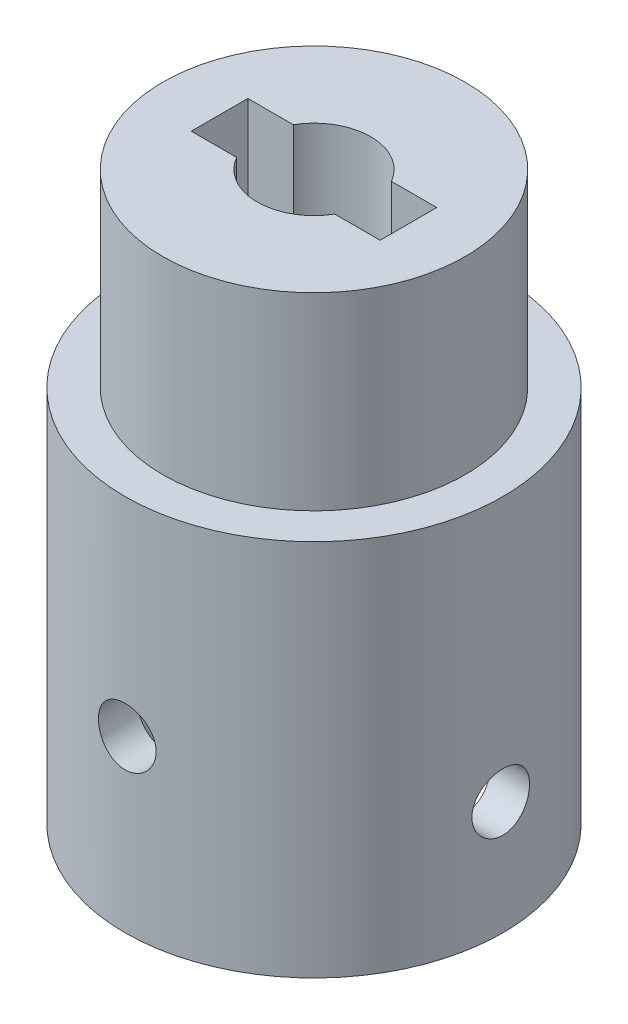
SolidWorks part; units mm, degrees
ref_plane "前视基准面" through (0, 0, 0) normal (0, 0, 1) x (1, 0, 0)
ref_plane "上视基准面" through (0, 0, 0) normal (0, 1, 0) x (1, 0, 0)
ref_plane "右视基准面" through (0, 0, 0) normal (1, 0, 0) x (0, 0, -1)
other "Configuration Table"
sketch "草图8" plane through (0, 0, 0) normal (0, 1, 0) x (1, 0, 0)
  circle A0 centre (79.6394, -3.747) radius 20
  circle A1 centre (79.6394, -3.747) radius 16
  dimension "D1" = 40
extrude "凸台-拉伸3" add sketch "草图8" along normal blind 20 separate body contours A1 region at (79.6394, 0, 3.747)
extrude "凸台-拉伸4" add sketch "草图8<4>" against normal blind 40 contours A0
sketch "草图8<4>" plane through (0, 0, 0) normal (0, 1, 0) x (1, 0, 0) same geometry as "草图8"
sketch "草图9" plane through (0, 20, 0) normal (0, 1, 0) x (1, 0, 0)
sketch "草图10" plane through (0, 20, 0) normal (0, 1, 0) x (1, 0, 0)
  line L0 (84.8356, -0.747) -> (89.6394, -0.747)
  line L1 (69.6394, -0.747) -> (74.4433, -0.747)
  line L2 (69.6394, -0.747) -> (69.6394, -6.747)
  line L3 (69.6394, -6.747) -> (74.4433, -6.747)
  line L4 (89.6394, -0.747) -> (89.6394, -6.747)
  line L5 (84.8356, -6.747) -> (89.6394, -6.747)
  arc A0 (74.4433, -6.747) -> (84.8356, -6.747) centre (79.6394, -3.747) ccw
  arc A1 (84.8356, -0.747) -> (74.4433, -0.747) centre (79.6394, -3.747) ccw
  dimension "D1" = 6
  dimension "D3" = 12
  dimension "D2" = 20
extrude "切除-拉伸6" cut sketch "草图10" against normal up to next
sketch "草图11" plane through (0, 0, 0) normal (0, 0, 1) x (1, 0, 0)
  line L0 (79.6394, -40) -> (79.6394, 0) construction
  line L2 (99.6394, 0) -> (59.6394, 0) construction
  circle A0 centre (79.6394, -22) radius 3.05
  dimension "D1" = 6.1
  dimension "D2" = 22
extrude "切除-拉伸7" cut sketch "草图11" against normal through all both and the other way through all
sketch "草图12" plane through (0, -40, 0) normal (0, -1, 0) x (1, 0, 0)
  circle A0 centre (79.6394, 3.747) radius 16.025
  dimension "D1" = 32.05
extrude "切除-拉伸8" cut sketch "草图12" against normal blind 30
sketch "草图13" plane through (0, 0, 0) normal (0, 0, 1) x (1, 0, 0)
  line L0 (0, 0) -> (0, 35.122) construction
ref_plane "基准面1" through (0, 0, 0) normal (1, 0, 0) x (0, 1, 0)
sketch "草图14" plane through (0, 0, 0) normal (1, 0, 0) x (0, 1, 0)
  line L0 (20, 3.747) -> (-40, 3.747) construction
  line L1 (20, -12.253) -> (20, 19.747) construction
  line L2 (-40, 23.747) -> (-40, -16.253) construction
  line L3 (0, -16.253) -> (0, 23.747) construction
  circle A0 centre (-28, 3.747) radius 3.05
  dimension "D1" = 6.1
  dimension "D2" = 28
extrude "切除-拉伸9" cut sketch "草图14" against normal through all both and the other way through all
